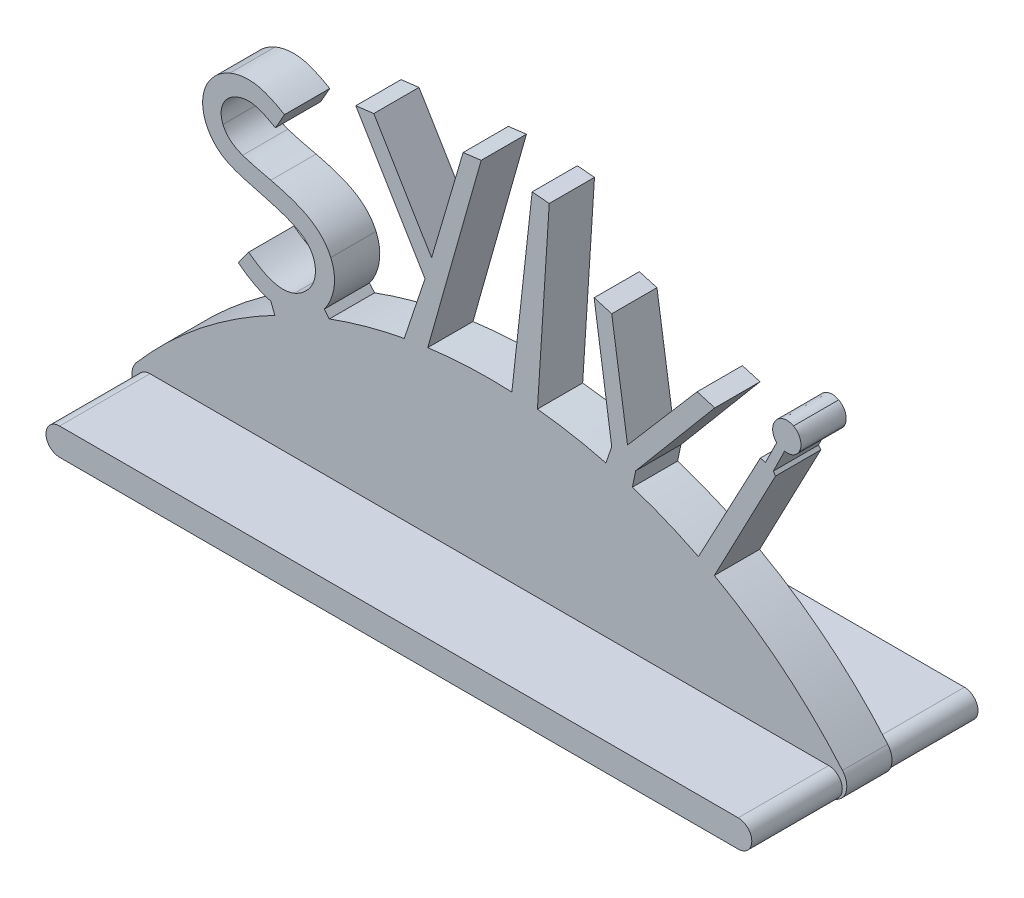
SolidWorks part; units mm, degrees
ref_plane "Front Plane" through (0, 0, 0) normal (0, 0, 1) x (1, 0, 0)
ref_plane "Top Plane" through (0, 0, 0) normal (0, 1, 0) x (1, 0, 0)
ref_plane "Right Plane" through (0, 0, 0) normal (1, 0, 0) x (0, 0, -1)
sketch "Sketch1" plane through (0, 0, 0) normal (0, 0, 1) x (1, 0, 0)
  line L0 (-78.7416, -19.9718) -> (-3.7416, -19.9718)
  line L5 (-68.9883, -1.4665) -> (-67.8385, 0.124)
  line L6 (-63.8801, 15.2602) -> (-64.8817, 13.4974)
  line L7 (-56.0018, 20.0511) -> (-54.0186, 20.2955)
  line L8 (-54.0186, 20.2955) -> (-47.6284, 9.6825)
  line L9 (-47.6284, 9.6825) -> (-44.1428, 21.5055)
  line L10 (-44.1428, 21.5055) -> (-42.1476, 21.7539)
  line L11 (-42.1476, 21.7539) -> (-48.0553, 0.8713)
  line L13 (-50.6488, 0.4558) -> (-48.3575, 7.3108)
  line L14 (-48.3575, 7.3108) -> (-56.0018, 20.0511)
  line L15 (-36.5154, 21.5492) -> (-34.6244, 21.385)
  line L16 (-34.6244, 21.385) -> (-35.9323, 1.0503)
  line L18 (-38.7573, 1.2656) -> (-36.5154, 21.5492)
  line L19 (-29.6639, 14.8429) -> (-27.7208, 14.278)
  line L20 (-27.7208, 14.278) -> (-25.974, 2.5873)
  line L21 (-25.974, 2.5873) -> (-18.2817, 11.5376)
  line L22 (-18.2817, 11.5376) -> (-16.3306, 10.9687)
  line L23 (-16.3306, 10.9687) -> (-25.0694, 0.58)
  line L27 (-9.6127, 7.8063) -> (-16.3802, -5.1014)
  line L29 (-18.1383, -4.1713) -> (-11.2874, 8.6957)
  line L30 (-9.5019, 11.0358) -> (-10.7431, 8.5134)
  line L31 (-10.7431, 8.5134) -> (-11.2874, 8.6957)
  line L32 (-8.6125, 10.6919) -> (-9.8658, 8.1449)
  line L33 (-9.8658, 8.1449) -> (-9.6127, 7.8063)
  line L36 (-27.7208, 1.5543) -> (-29.6639, 14.8429)
  line L38 (-27.7208, 1.5543) -> (-28.3599, -0.3179)
  line L39 (-25.0694, 0.58) -> (-25.433, -1.1709)
  line L40 (-65.3906, -3.3429) -> (-64.9583, -4.486)
  line L41 (-59.4861, -1.158) -> (-58.9282, -1.8197)
  arc A0 (-80.2629, -16.6735) -> (-64.9583, -4.486) centre (-41.2416, -49.9718) cw
  arc A1 (-80.2629, -16.6735) -> (-78.7416, -19.9718) centre (-78.7416, -17.9718) ccw
  arc A2 (-3.7416, -19.9718) -> (-2.2202, -16.6735) centre (-3.7416, -17.9718) ccw
  arc A3 (-6.9845, 11.4721) -> (-8.6125, 10.6919) centre (-8.3069, 12.1429) cw
  arc A4 (-9.7329, 12.9305) -> (-9.5019, 11.0358) centre (-8.3069, 12.1429) ccw
  arc A5 (-16.3802, -5.1014) -> (-2.2202, -16.6735) centre (-41.2416, -49.9718) cw
  arc A9 (-35.9323, 1.0503) -> (-28.3599, -0.3179) centre (-41.2416, -49.9718) cw
  arc A11 (-48.0553, 0.8713) -> (-38.7573, 1.2656) centre (-41.2416, -49.9718) cw
  arc A13 (-58.9282, -1.8197) -> (-50.6488, 0.4558) centre (-41.2416, -49.9718) cw
  arc A16 (-25.433, -1.1709) -> (-18.1383, -4.1713) centre (-41.2416, -49.9718) cw
  spline S0 degree 3 poles (-67.8385, 0.124) (-67.3926, -0.2301) (-66.7195, -0.7013) (-65.7793, -1.1633) (-65.1296, -1.3912) (-64.5037, -1.5262) (-63.7045, -1.5617) (-63.1259, -1.4261) (-62.7704, -1.2782) knots 0 0 0 0 0.30954 0.444192 0.567856 0.682676 0.790858 1 1 1 1
  spline S1 degree 3 poles (-62.7704, -1.2782) (-62.4702, -1.1504) (-62.0456, -0.9055) (-61.5514, -0.4825) (-61.2262, -0.1233) (-60.9446, 0.2655) (-60.7277, 0.6803) (-60.5718, 1.1099) (-60.4852, 1.5519) (-60.4574, 1.9937) (-60.4946, 2.5732) (-60.6072, 2.9934) (-60.7231, 3.257) knots 0 0 0 0 0.176818 0.263606 0.351769 0.438976 0.523188 0.604727 0.685956 0.766492 0.844138 1 1 1 1
  spline S2 degree 3 poles (-60.7231, 3.257) (-60.8512, 3.5677) (-61.2451, 4.1562) (-61.7943, 4.6015) (-62.1053, 4.7915) knots 0 0 0 0 0.478763 1 1 1 1
  spline S3 degree 3 poles (-62.1053, 4.7915) (-62.3569, 4.9515) (-62.7773, 5.1619) (-63.38, 5.4204) (-63.9009, 5.6269) (-64.4744, 5.8203) (-65.336, 6.0859) (-66.0111, 6.2709) (-66.4803, 6.386) knots 0 0 0 0 0.19113 0.301354 0.421094 0.550707 0.689839 1 1 1 1
  spline S4 degree 3 poles (-66.4803, 6.386) (-66.9392, 6.5026) (-67.596, 6.6674) (-68.4196, 6.9112) (-68.9408, 7.0748) (-69.3958, 7.2288) (-69.8747, 7.411) (-70.1931, 7.5611) (-70.3785, 7.6681) knots 0 0 0 0 0.345397 0.49364 0.626407 0.74376 0.843968 1 1 1 1
  spline S5 degree 3 poles (-70.3785, 7.6681) (-70.6277, 7.8056) (-70.9723, 8.0476) (-71.4, 8.4031) (-71.6823, 8.693) (-71.9429, 8.9985) (-72.2456, 9.4386) (-72.435, 9.7929) (-72.538, 10.0399) knots 0 0 0 0 0.260808 0.386135 0.510166 0.632036 0.754529 1 1 1 1
  spline S6 degree 3 poles (-72.538, 10.0399) (-72.6999, 10.4231) (-72.8794, 11.0215) (-72.945, 11.8438) (-72.9072, 12.454) (-72.7934, 13.0531) (-72.5943, 13.6309) (-72.3111, 14.1769) (-71.9529, 14.6902) (-71.5307, 15.1602) (-70.8874, 15.7195) (-70.325, 16.0336) (-69.9338, 16.2058) knots 0 0 0 0 0.16726 0.248534 0.330233 0.412205 0.492804 0.574873 0.658521 0.743628 0.828073 1 1 1 1
  spline S7 degree 3 poles (-69.9338, 16.2058) (-69.5133, 16.3811) (-68.8532, 16.5772) (-67.9419, 16.6444) (-67.3653, 16.6164) (-66.8922, 16.5402) (-66.5138, 16.4571) (-66.1183, 16.3351) (-65.7062, 16.1814) (-65.2734, 16.0004) (-64.6565, 15.7018) (-64.1893, 15.4507) (-63.8801, 15.2602) knots 0 0 0 0 0.214162 0.319804 0.427786 0.484271 0.544657 0.609512 0.678342 0.751117 0.829636 1 1 1 1
  spline S8 degree 3 poles (-64.8817, 13.4974) (-65.1313, 13.6426) (-65.4985, 13.842) (-65.982, 14.0766) (-66.3097, 14.2201) (-66.6133, 14.3423) (-66.8959, 14.435) (-67.1566, 14.5045) (-67.4741, 14.5631) (-67.8557, 14.5885) (-68.4582, 14.5536) (-68.8948, 14.4229) (-69.1726, 14.3067) knots 0 0 0 0 0.190224 0.275245 0.354059 0.425967 0.490811 0.54994 0.603624 0.70332 0.801202 1 1 1 1
  spline S9 degree 3 poles (-69.1726, 14.3067) (-69.5118, 14.1617) (-69.9838, 13.873) (-70.4541, 13.3278) (-70.6998, 12.8725) (-70.8601, 12.3909) (-70.9247, 11.7228) (-70.8168, 11.2274) (-70.683, 10.9213) knots 0 0 0 0 0.267899 0.392815 0.517555 0.64059 0.758267 1 1 1 1
  spline S10 degree 3 poles (-70.683, 10.9213) (-70.6013, 10.7227) (-70.4406, 10.4429) (-70.1767, 10.102) (-69.9455, 9.8613) (-69.6678, 9.6387) (-69.2013, 9.3444) (-68.808, 9.1578) (-68.5236, 9.0463) knots 0 0 0 0 0.218443 0.327061 0.438707 0.557731 0.688726 1 1 1 1
  spline S11 degree 3 poles (-68.5236, 9.0463) (-68.3966, 8.9969) (-68.1679, 8.9327) (-67.8227, 8.8296) (-67.4625, 8.7419) (-67.0401, 8.625) (-66.3395, 8.4609) (-65.7844, 8.3188) (-65.3906, 8.229) knots 0 0 0 0 0.125996 0.219956 0.333661 0.469275 0.62588 1 1 1 1
  spline S12 degree 3 poles (-65.3906, 8.229) (-64.9026, 8.1134) (-64.1973, 7.93) (-63.3008, 7.6486) (-62.7028, 7.4377) (-62.1575, 7.2153) (-61.659, 6.9959) (-61.2163, 6.7571) (-60.8204, 6.5118) (-60.4642, 6.2561) (-60.1371, 5.992) (-59.8421, 5.7111) (-59.5718, 5.4208) (-59.3258, 5.1222) (-59.043, 4.7025) (-58.8667, 4.3688) (-58.768, 4.1384) knots 0 0 0 0 0.186086 0.270249 0.348617 0.421314 0.488738 0.550594 0.607797 0.661428 0.713205 0.763683 0.812421 0.860328 0.907059 1 1 1 1
  spline S13 degree 3 poles (-58.768, 4.1384) (-58.6324, 3.8168) (-58.4684, 3.3191) (-58.3661, 2.6346) (-58.3467, 2.1215) (-58.3794, 1.6062) (-58.4633, 1.0864) (-58.6065, 0.5642) (-58.7968, 0.0436) (-59.0337, -0.4603) (-59.2715, -0.8583) (-59.4304, -1.0833) (-59.4861, -1.158) knots 0 0 0 0 0.121781 0.181574 0.240755 0.300472 0.361329 0.424017 0.48898 0.554383 0.617868 0.650349 0.650349 0.650349 0.650349
  spline S15 degree 3 poles (-7.6335, 13.5835) (-7.4508, 13.4896) (-7.2138, 13.291) (-6.979, 12.952) (-6.8695, 12.6611) (-6.8022, 12.3585) (-6.7964, 11.948) (-6.8867, 11.651) (-6.9845, 11.4721) knots 0 0 0 0 0.250094 0.372592 0.501081 0.628126 0.750821 1 1 1 1
  spline S16 degree 3 poles (-65.3906, -3.3429) (-65.4833, -3.3237) (-65.7282, -3.2658) (-66.1222, -3.1398) (-66.5799, -2.9635) (-67.0427, -2.7394) (-67.5218, -2.4853) (-68.1816, -2.0699) (-68.6705, -1.7238) (-68.9883, -1.4665) knots 0.46978 0.46978 0.46978 0.46978 0.506587 0.567506 0.630461 0.697109 0.767257 0.841164 1 1 1 1
  spline S18 degree 3 poles (-9.7329, 12.9305) (-9.6428, 13.1147) (-9.4437, 13.3508) (-9.1063, 13.5837) (-8.8163, 13.6965) (-8.5144, 13.7591) (-8.1054, 13.7772) (-7.8129, 13.6719) (-7.6335, 13.5835) knots 0 0 0 0 0.250258 0.373276 0.500787 0.62998 0.751587 1 1 1 1
  dimension "D1" = 2
  dimension "D2" = 2
  dimension "D4" = 30
  dimension "D3" = 75
extrude "Boss-Extrude2" add sketch "Sketch1" along normal blind 5
sketch "Sketch3" plane through (0, 0, 5) normal (0, 0, 1) x (1, 0, 0)
  line L1 (-78.7416, -19.9718) -> (-3.7416, -19.9718)
  line L5 (-78.7416, -16.9718) -> (-3.7416, -16.9718)
  arc A1 (-3.7416, -19.9718) -> (-3.7416, -16.9718) centre (-3.7416, -18.4718) ccw
  arc A2 (-78.7416, -19.9718) -> (-78.7416, -16.9718) centre (-78.7416, -18.4718) cw
extrude "Boss-Extrude3" add sketch "Sketch3" along normal blind 10
extrude "Boss-Extrude4" add sketch "Sketch3<2>" against normal blind 15
sketch "Sketch3<2>" plane through (0, 0, 5) normal (0, 0, 1) x (1, 0, 0) same geometry as "Sketch3"
